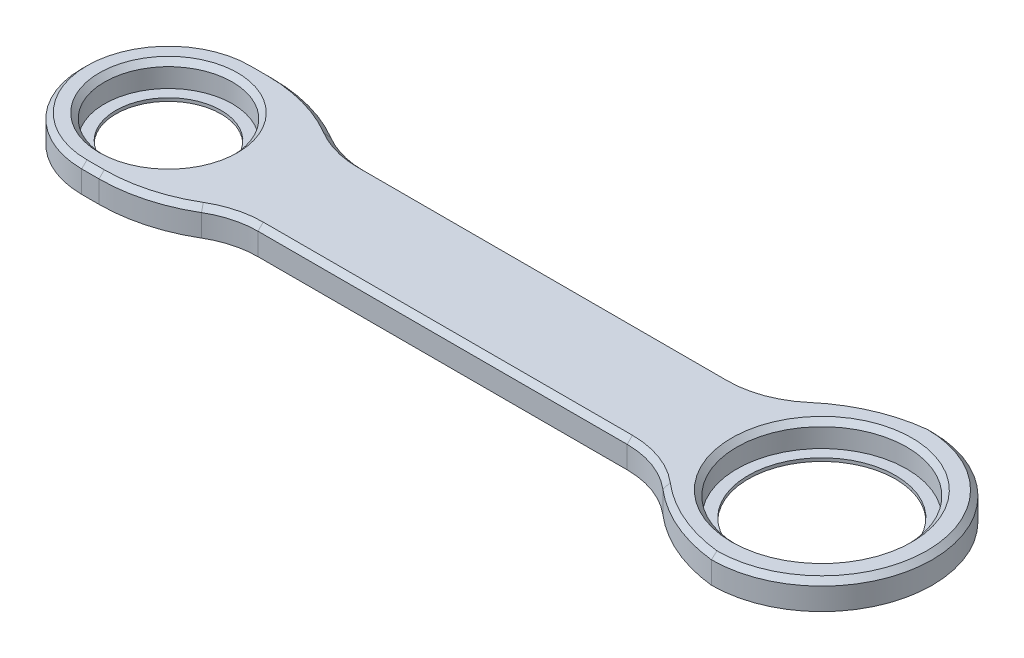
SolidWorks part; units mm, degrees
ref_plane "Front Plane" through (0, 0, 0) normal (0, 0, 1) x (1, 0, 0)
ref_plane "Top Plane" through (0, 0, 0) normal (0, 1, 0) x (1, 0, 0)
ref_plane "Right Plane" through (0, 0, 0) normal (1, 0, 0) x (0, 0, -1)
sketch "Sketch1" plane through (0, 0, 0) normal (0, 1, 0) x (1, 0, 0)
  line L0 (62.125, 0) -> (-62.125, 0) construction
  line L1 (62.125, -21) -> (-62.125, -21)
  line L2 (62.125, 21) -> (-62.125, 21)
  line L3 (-35.1066, 26.5458) -> (35.1066, 26.5458) construction
  line L4 (-35.1066, 43.0915) -> (35.1066, 43.0915)
  line L5 (-35.1066, 10) -> (35.1066, 10)
  line L6 (-35.1066, -26.5458) -> (35.1066, -26.5458) construction
  line L7 (-35.1066, -10) -> (35.1066, -10)
  line L8 (-35.1066, -43.0915) -> (35.1066, -43.0915)
  arc A0 (62.125, -21) -> (62.125, 21) centre (62.125, 0) ccw
  arc A1 (-62.125, 21) -> (-62.125, -21) centre (-62.125, 0) ccw
  circle A2 centre (-62.125, 0) radius 12.15
  arc A3 (-35.1066, 43.0915) -> (-35.1066, 10) centre (-35.1066, 26.5458) ccw
  arc A4 (35.1066, 10) -> (35.1066, 43.0915) centre (35.1066, 26.5458) ccw
  arc A5 (-35.1066, -10) -> (-35.1066, -43.0915) centre (-35.1066, -26.5458) ccw
  arc A6 (35.1066, -43.0915) -> (35.1066, -10) centre (35.1066, -26.5458) ccw
  circle A7 centre (62.125, 0) radius 16.15
  point P2 (0, 0)
  point P12 (0, 26.5458)
  point P19 (0, -26.5458)
  point P24 (35.1066, -27.5458)
  dimension "D2" = 24.3
  dimension "D3" = 21
  dimension "D6" = 32.3
  dimension "D1" = 124.25
  dimension "D4" = 10
  dimension "D5" = 10
extrude "Boss-Extrude1" add sketch "Sketch1" along normal blind 5.2 contours A6 L1 A0 L2 A4 L5 A3 A1 A5 L7 A7 A2 region at (-6.7439, 0, 0)
sketch "Sketch4" plane through (0, 5.2, 0) normal (0, 1, 0) x (1, 0, 0)
  line L0 (-62.125, 16.5) -> (-40.411, 16.5)
  line L1 (-40.411, 16.5) -> (-43.408, 33.3429)
  line L2 (-43.408, 33.3429) -> (-92.9845, 23.091)
  line L3 (-92.9845, 23.091) -> (-92.9845, -9.501)
  line L4 (-92.9845, -9.501) -> (-86.7109, -27.0976)
  line L5 (-86.7109, -27.0976) -> (-50.7369, -31.9731)
  line L6 (-50.7369, -31.9731) -> (-37.8994, -29.5848)
  line L7 (-37.8994, -29.5848) -> (-38.9705, -16.5)
  line L8 (-38.9705, -16.5) -> (-62.125, -16.5)
  arc A0 (-62.125, 16.5) -> (-62.125, -16.5) centre (-62.125, 0) ccw
  arc A1 (-35.1066, -10) -> (-35.1066, -43.0915) centre (-35.1066, -26.5458) ccw construction
  point P1 (-40.411, 16.5)
  dimension "D1" = 16.5
extrude "Cut-Extrude1" cut sketch "Sketch4" against normal through all
fillet "Fillet1" radius 30 4 edges at (50.6953, 2.6, -21) (50.6953, 2.6, 21) (-48.2537, 2.6, -16.5) (-48.2537, 2.6, 16.5)
chamfer "Chamfer1" distance 1 angle 45 16 edges at (62.125, 5.2, 16.15) (-62.125, 5.2, 12.15) (0, 5.2, -10) (-39.4787, 5.2, -10.5881) (40.8393, 5.2, -11.0249) (53.4628, 5.2, -18.7141) (83.125, 5.2, 0) (53.4628, 5.2, 18.7141) (-39.4787, 5.2, 10.5881) (40.8393, 5.2, 11.0249) (0, 5.2, 10) (-50.9037, 5.2, -15.4337) (-60.478, 5.2, -16.5) (-78.625, 5.2, 0) (-60.478, 5.2, 16.5) (-50.9037, 5.2, 15.4337)
sketch "Sketch2" plane through (0, 0, 0) normal (0, -1, 0) x (1, 0, 0)
  circle A0 centre (-62.125, 0) radius 10
  circle A1 centre (-62.125, 0) radius 14.7553
  circle A2 centre (62.125, 0) radius 14
  circle A3 centre (62.125, 0) radius 19.0252
  dimension "D1" = 20
  dimension "D2" = 28
extrude "Boss-Extrude2" add sketch "Sketch2" against normal blind 0.6
sketch "Sketch3" plane through (0, 5.4, 0) normal (0, 1, 0) x (1, 0, 0)
  line L0 (77.77, 28.8659) -> (77.77, -26.5149) construction
  line L1 (0, 0) -> (86.87, 0) construction
  line L2 (77.775, 17.2779) -> (77.775, -15.919) construction
  circle A1 centre (61.625, 0) radius 16.15 construction
  dimension "D1" = 86.87
  dimension "D2" = 9.1
